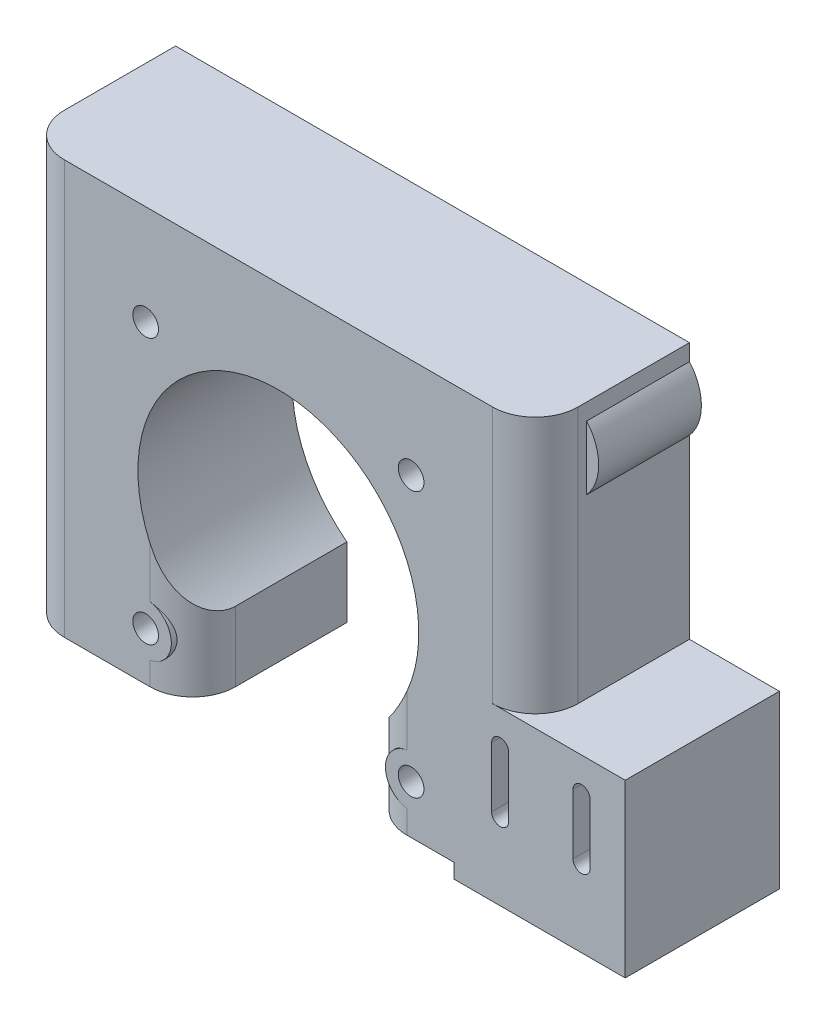
SolidWorks part; units mm, degrees
material "ABS"
ref_plane "Спереди" through (0, 0, 0) normal (0, 0, 1) x (1, 0, 0)
ref_plane "Сверху" through (0, 0, 0) normal (0, 1, 0) x (1, 0, 0)
ref_plane "Справа" through (0, 0, 0) normal (1, 0, 0) x (0, 0, -1)
sketch "Эскиз1" plane through (0, 0, 0) normal (0, 0, 1) x (1, 0, 0)
  line L1 (30, -17.8) -> (-30, -17.8)
  line L2 (30, -17.8) -> (30, 24.5)
  line L3 (30, 24.5) -> (-30, 24.5)
  line L4 (-30, -17.8) -> (-30, 24.5)
  line L5 (30, -17.8) -> (-30, 24.5) construction
  line L6 (30, 24.5) -> (-30, -17.8) construction
  line L8 (0, 30.5) -> (0, -17.8) construction
  line L9 (-10, -17.8) -> (-10, -9.6485)
  line L11 (10, -9.6485) -> (10, -17.8)
  line L12 (16.9074, 24.5) -> (-16.9074, 24.5) construction
  arc A0 (10, -9.6485) -> (-10, -9.6485) centre (0, 3.35) ccw
  circle A1 centre (0, 3.35) radius 16.4 construction
  circle A5 centre (15.5, 18.85) radius 1.5
  circle A6 centre (-15.5, 18.85) radius 1.5
  circle A7 centre (-15.5, -12.15) radius 1.5
  circle A8 centre (15.5, -12.15) radius 1.5
  dimension "D3" = 3
  dimension "D1" = 60
  dimension "D2" = 20
extrude "Бобышка-Вытянуть1" add sketch "Эскиз1" along normal blind 18 contours L3 L4 L1 L9 A0 L11 L2 region at (20, -17.0659, 0)
sketch "Эскиз9" plane through (0, 24.5, 0) normal (0, 1, 0) x (1, 0, 0)
  line L1 (-30, -18) -> (30, -18)
  line L2 (-30, -18) -> (-30, 0)
  line L3 (-30, 0) -> (30, 0)
  line L4 (30, -18) -> (30, 0)
extrude "Бобышка-Вытянуть4" add sketch "Эскиз9" along normal blind 6
fillet "Скругление1" radius 5 4 edges at (-30, 6.35, 18) (30, 6.35, 18) (10, -13.7242, 18) (-10, -13.7242, 18)
sketch "Эскиз2" plane through (0, 0, 18) normal (0, 0, 1) x (1, 0, 0)
  circle A0 centre (-15.5, -12.15) radius 3
  circle A1 centre (15.5, -12.15) radius 3
  circle A2 centre (-15.5, -12.15) radius 1.5
  circle A3 centre (15.5, -12.15) radius 1.5
  dimension "D1" = 6
  dimension "D2" = 6
extrude "Бобышка-Вытянуть2" add sketch "Эскиз2" against normal blind 4
sketch "Эскиз3" plane through (0, -17.8, 0) normal (0, -1, 0) x (1, 0, 0)
  circle A0 centre (-21, 12.5) radius 1.5
  circle A1 centre (21, 12.5) radius 1.5
  dimension "D1" = 3
extrude "Вырез-Вытянуть1" cut sketch "Эскиз3" against normal blind 8
sketch "Эскиз5" plane through (0, 0, 18) normal (0, 0, 1) x (1, 0, 0)
  line L0 (20.5, -4.5) -> (40.5, -14.5) construction
  line L1 (40.5, -14.5) -> (40.5, -4.5) construction
  line L2 (40.5, 0.5) -> (20.5, 0.5)
  line L3 (40.5, 0.5) -> (40.5, -19.5)
  line L4 (40.5, -19.5) -> (20.5, -19.5)
  line L5 (20.5, 0.5) -> (20.5, -19.5)
  line L6 (40.5, 0.5) -> (20.5, -19.5) construction
  line L7 (40.5, -19.5) -> (20.5, 0.5) construction
  point P4 (30.5, -9.5)
  dimension "D1" = 20
extrude "Бобышка-Вытянуть3" add sketch "Эскиз5" against normal up to surface (18 mm away) up to face at (17, -12.15, 0)
sketch "Эскиз6" plane through (0, -17.8, 0) normal (0, -1, 0) x (1, 0, 0)
  circle A0 centre (21, 12.5) radius 1.5
  dimension "D1" = 3
extrude "Вырез-Вытянуть6" cut sketch "Эскиз6" against normal up to surface (8 mm away) up to face at (20, -9.8, 12.5)
sketch "Эскиз7" plane through (0, 0, 18) normal (0, 0, 1) x (1, 0, 0)
  line L0 (25.9, -10.4858) -> (25.9, -3.4858) construction
  line L1 (24.9, -10.4858) -> (24.9, -3.4858)
  line L2 (26.9, -10.4858) -> (26.9, -3.4858)
  line L3 (35.4, -10.4858) -> (35.4, -3.4858) construction
  line L4 (34.4, -10.4858) -> (34.4, -3.4858)
  line L5 (36.4, -10.4858) -> (36.4, -3.4858)
  arc A0 (24.9, -10.4858) -> (26.9, -10.4858) centre (25.9, -10.4858) ccw
  arc A1 (26.9, -3.4858) -> (24.9, -3.4858) centre (25.9, -3.4858) ccw
  arc A2 (34.4, -10.4858) -> (36.4, -10.4858) centre (35.4, -10.4858) ccw
  arc A3 (36.4, -3.4858) -> (34.4, -3.4858) centre (35.4, -3.4858) ccw
  point P2 (25.9, -6.9858)
  point P7 (35.4, -6.9858)
  dimension "D1" = 2
  dimension "D2" = 7
extrude "Вырез-Вытянуть7" cut sketch "Эскиз7" against normal blind 6
sketch "Эскиз8" plane through (0, 0, 0) normal (0, 0, -1) x (-1, 0, 0)
  line L1 (29.7915, -11.8) -> (27.7707, -8.3)
  line L2 (27.7707, -8.3) -> (23.7293, -8.3)
  line L3 (23.7293, -8.3) -> (21.7085, -11.8)
  line L4 (21.7085, -11.8) -> (23.7293, -15.3)
  line L5 (23.7293, -15.3) -> (27.7707, -15.3)
  line L6 (27.7707, -15.3) -> (29.7915, -11.8)
  line L7 (-21.7085, -11.8) -> (-23.7293, -8.3)
  line L8 (-23.7293, -8.3) -> (-27.7707, -8.3)
  line L9 (-27.7707, -8.3) -> (-29.7915, -11.8)
  line L10 (-29.7915, -11.8) -> (-27.7707, -15.3)
  line L11 (-27.7707, -15.3) -> (-23.7293, -15.3)
  line L12 (-23.7293, -15.3) -> (-21.7085, -11.8)
  line L13 (-21.7085, 24.85) -> (-23.7293, 28.35)
  line L14 (-23.7293, 28.35) -> (-27.7707, 28.35)
  line L15 (-27.7707, 28.35) -> (-29.7915, 24.85)
  line L16 (-29.7915, 24.85) -> (-27.7707, 21.35)
  line L17 (-27.7707, 21.35) -> (-23.7293, 21.35)
  line L18 (-23.7293, 21.35) -> (-21.7085, 24.85)
  line L19 (29.7915, 24.85) -> (27.7707, 28.35)
  line L20 (27.7707, 28.35) -> (23.7293, 28.35)
  line L21 (23.7293, 28.35) -> (21.7085, 24.85)
  line L22 (21.7085, 24.85) -> (23.7293, 21.35)
  line L23 (23.7293, 21.35) -> (27.7707, 21.35)
  line L24 (27.7707, 21.35) -> (29.7915, 24.85)
  circle A0 centre (25.75, -11.8) radius 3.5 construction
  circle A1 centre (-25.75, -11.8) radius 3.5 construction
  circle A2 centre (-25.75, 24.85) radius 3.5 construction
  circle A3 centre (25.75, 24.85) radius 3.5 construction
  dimension "D1" = 7
extrude "Вырез-Вытянуть8" cut sketch "Эскиз8" against normal blind 3 from offset 4 offset against normal yes
sketch "Эскиз10" plane through (0, 0, 0) normal (0, 0, -1) x (-1, 0, 0)
  line L0 (30, 30.5) -> (-30, 30.5) construction
  circle A0 centre (25.75, 24.85) radius 4.0415
  circle A1 centre (-25.75, 24.85) radius 4.0415
  circle A2 centre (-25.75, -11.8) radius 4.0415
  circle A3 centre (25.75, -11.8) radius 4.0415
  circle A4 centre (25.75, -11.8) radius 5.65
  circle A5 centre (25.75, 24.85) radius 5.65
  circle A6 centre (-25.75, 24.85) radius 5.65
  circle A7 centre (-25.75, -11.8) radius 5.65
  dimension "D1" = 8.0829
extrude "Бобышка-Вытянуть5" add sketch "Эскиз10" against normal blind 12
sketch "Эскиз11" plane through (0, 0, 0) normal (0, 0, -1) x (-1, 0, 0)
  circle A0 centre (-25.75, 24.85) radius 2
  circle A1 centre (25.75, 24.85) radius 2
  circle A2 centre (25.75, -11.8) radius 2
  circle A3 centre (-25.75, -11.8) radius 2
  dimension "D1" = 4
extrude "Вырез-Вытянуть9" cut sketch "Эскиз11" against normal blind 10
